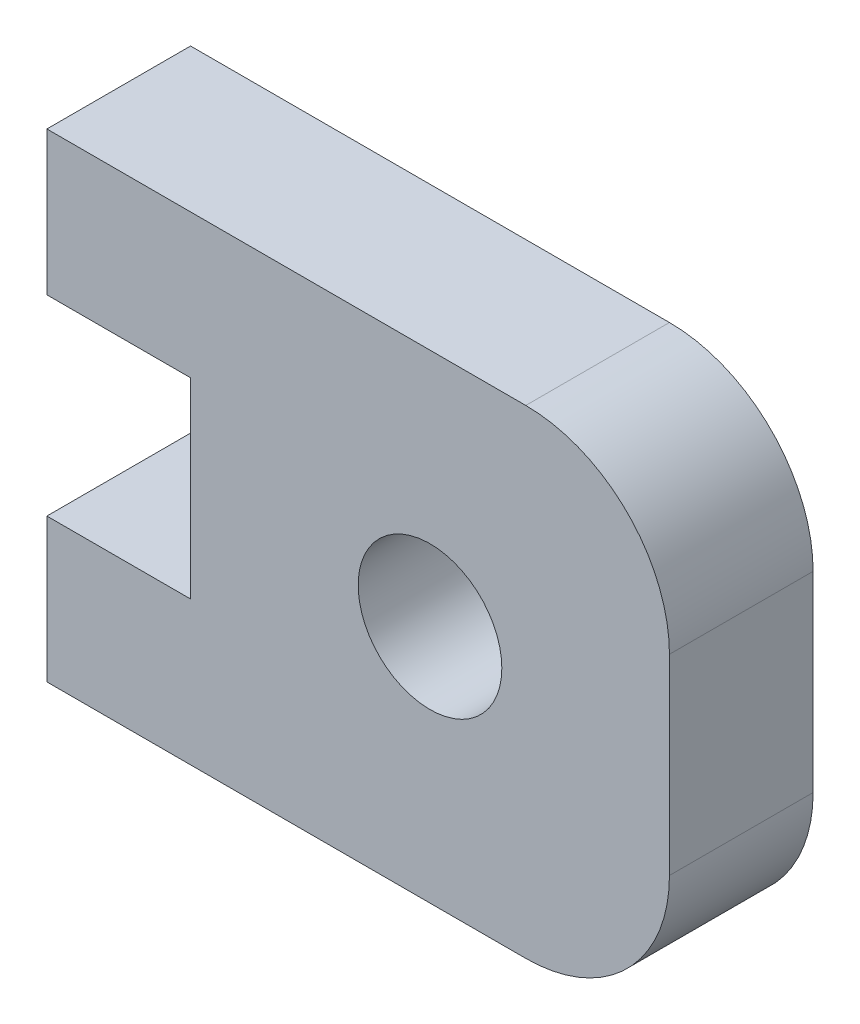
SolidWorks part; units mm, degrees
ref_plane "Front Plane" through (0, 0, 0) normal (0, 0, 1) x (1, 0, 0)
ref_plane "Top Plane" through (0, 0, 0) normal (0, 1, 0) x (1, 0, 0)
ref_plane "Right Plane" through (0, 0, 0) normal (1, 0, 0) x (0, 0, -1)
sketch "Sketch1" plane through (0, 0, 0) normal (0, 0, 1) x (1, 0, 0)
  line L0 (0, 10) -> (10, 10)
  line L1 (10, 0) -> (0, 0)
  line L2 (0, 0) -> (0, 3)
  line L3 (0, 3) -> (3, 3)
  line L6 (0, 10) -> (0, 7)
  line L7 (0, 7) -> (3, 7)
  line L10 (3, 7) -> (3, 3)
  line L12 (13, 7) -> (13, 3)
  arc A0 (10, 0) -> (13, 3) centre (10, 3) ccw
  arc A1 (10, 10) -> (13, 7) centre (10, 7) cw
  circle A2 centre (8, 5) radius 1.5
  point P11 (13, 0)
  point P14 (13, 10)
  dimension "D4" = 3
  dimension "D5" = 3
  dimension "D6" = 5
  dimension "D7" = 5
  dimension "D1" = 13
  dimension "D2" = 10
  dimension "D3" = 3
extrude "Boss-Extrude1" add sketch "Sketch1" along normal blind 3
